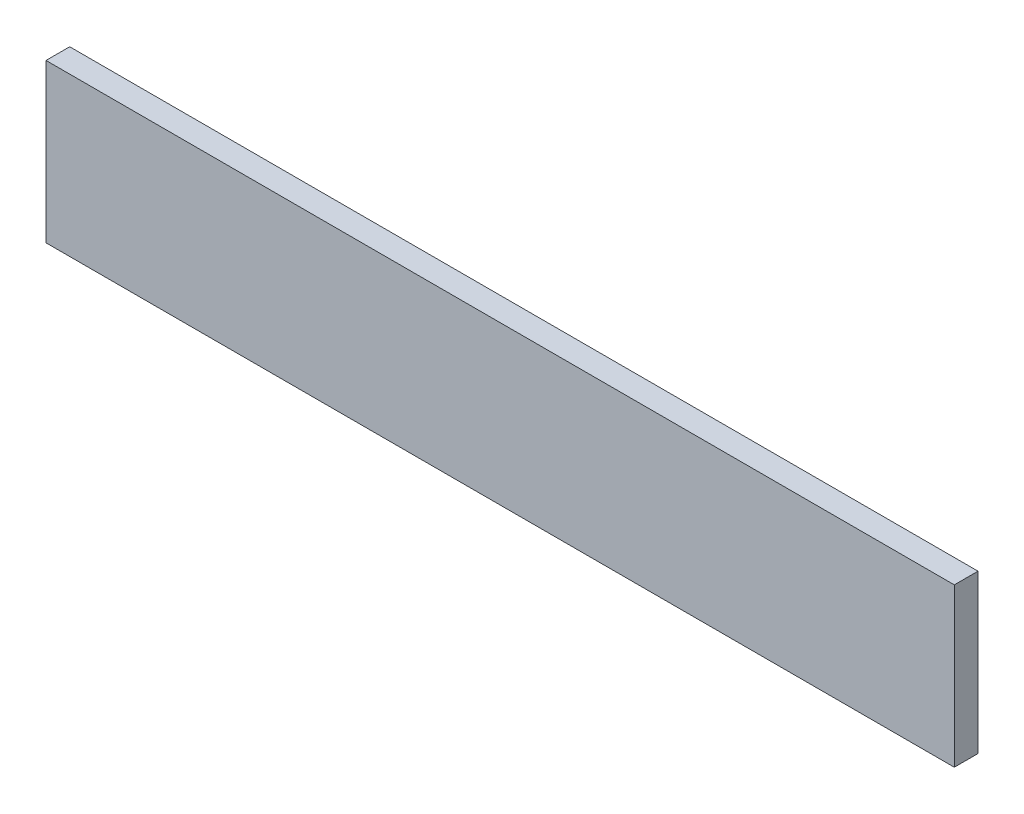
SolidWorks part; units mm, degrees
ref_plane "Front Plane" through (0, 0, 0) normal (0, 0, 1) x (1, 0, 0)
ref_plane "Top Plane" through (0, 0, 0) normal (0, 1, 0) x (1, 0, 0)
ref_plane "Right Plane" through (0, 0, 0) normal (1, 0, 0) x (0, 0, -1)
sketch "Sketch1" plane through (0, 0, 0) normal (0, 0, 1) x (1, 0, 0)
  line L1 (0, 0) -> (730.25, 0)
  line L2 (0, 0) -> (0, 127)
  line L3 (0, 127) -> (730.25, 127)
  line L4 (730.25, 0) -> (730.25, 127)
  dimension "D1" = 730.25
  dimension "D2" = 127
extrude "Boss-Extrude1" add sketch "Sketch1" along normal blind 19.05
